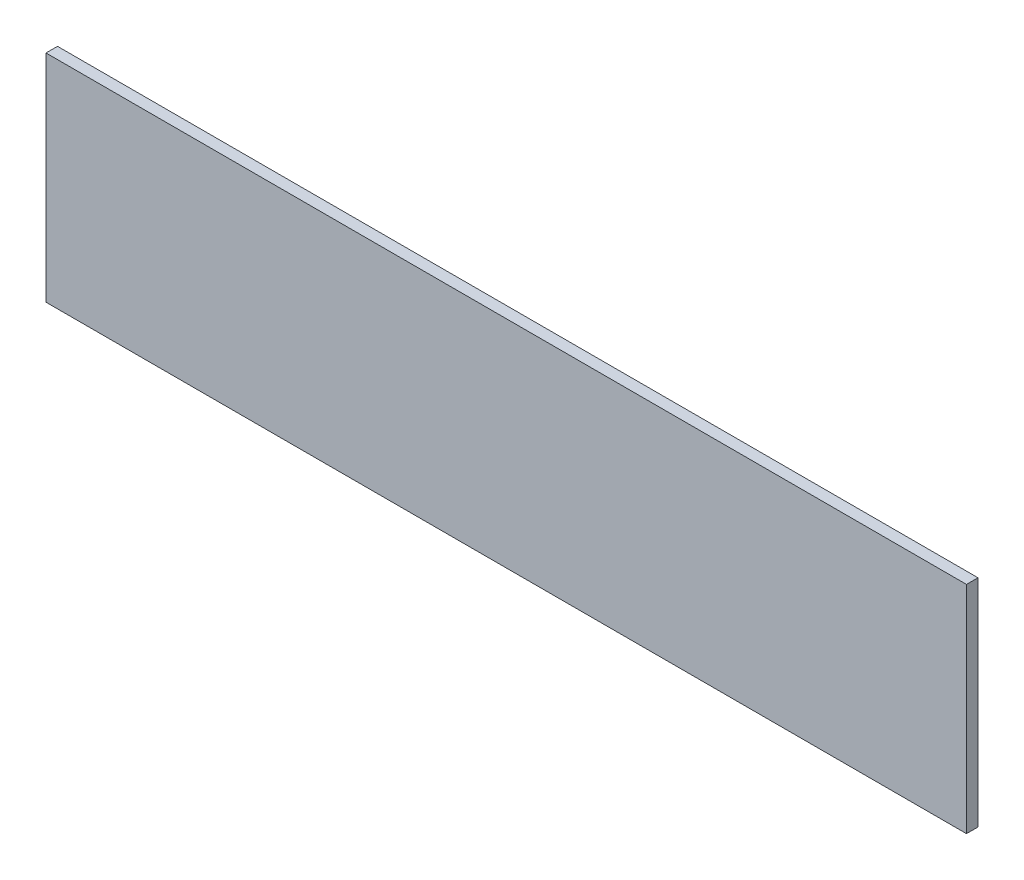
SolidWorks part; units mm, degrees
ref_plane "Front Plane" through (0, 0, 0) normal (0, 0, 1) x (1, 0, 0)
ref_plane "Top Plane" through (0, 0, 0) normal (0, 1, 0) x (1, 0, 0)
ref_plane "Right Plane" through (0, 0, 0) normal (1, 0, 0) x (0, 0, -1)
sketch "Sketch1" plane through (0, 0, 0) normal (0, 0, 1) x (1, 0, 0)
  line L1 (-120, 28.1436) -> (120, 28.1436)
  line L2 (-120, 28.1436) -> (-120, -28.1436)
  line L3 (-120, -28.1436) -> (120, -28.1436)
  line L4 (120, 28.1436) -> (120, -28.1436)
  line L5 (0, 28.1436) -> (0, -28.1436) construction
  point P0 (0, 0)
  dimension "D1" = 240
extrude "Boss-Extrude1" add sketch "Sketch1" along normal blind 3
sketch "Sketch2" plane through (0, 0, 3) normal (0, 0, 1) x (1, 0, 0)
  line L0 (-120, -12.9087) -> (120, -12.9087) construction
  line L1 (-18.5, 3.0913) -> (-3.5, 3.0913) construction
  line L2 (-18.5, 3.0913) -> (-18.5, -12.9087) construction
  line L3 (-18.5, -12.9087) -> (-3.5, -12.9087) construction
  line L4 (-3.5, 3.0913) -> (-3.5, -12.9087) construction
  line L5 (-120, 28.1436) -> (-120, -28.1436) construction
  line L6 (120, -28.1436) -> (120, 28.1436) construction
  line L7 (-20, -14.4087) -> (-2, -14.4087)
  line L8 (-2, 4.5913) -> (-2, -14.4087)
  line L9 (-20, 4.5913) -> (-2, 4.5913)
  line L10 (-20, 4.5913) -> (-20, -14.4087)
  line L11 (-120, -28.1436) -> (120, -28.1436) construction
  point P10 (-11, 3.0913)
  dimension "D1" = 15
  dimension "D2" = 16
  dimension "D3" = 11
  dimension "D5" = 15.2349
  dimension "D4" = 1.5
